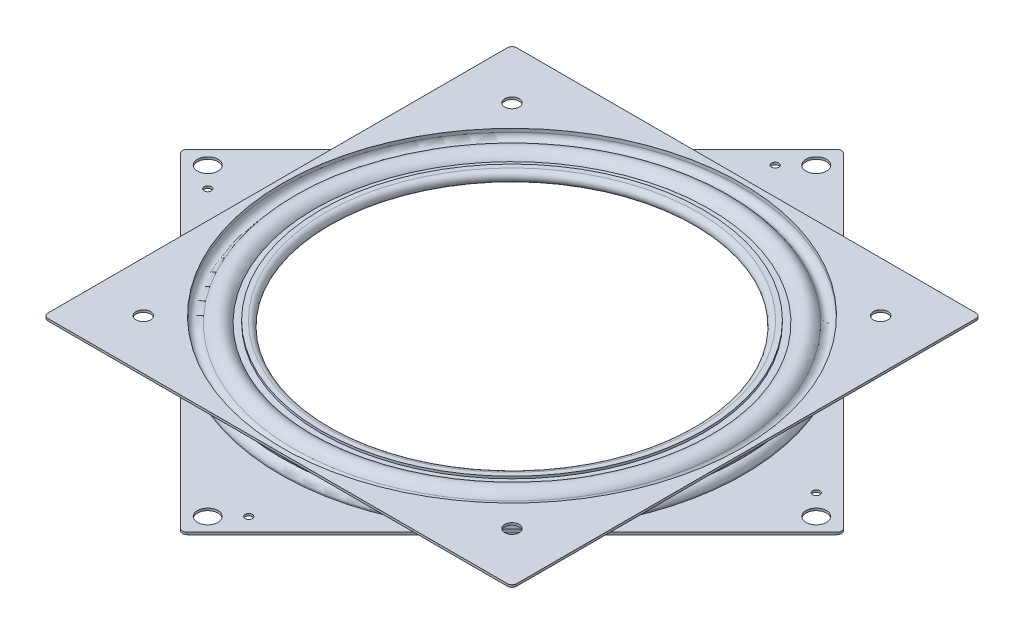
SolidWorks part; units mm, degrees
note: The reader was unsure of these and kept them because the rebuilt part matched: shared geometry of "Sketch3<3>".
material "Galvanized Steel"
ref_plane "Front Plane" through (0, 0, 0) normal (0, 0, 1) x (1, 0, 0)
ref_plane "Top Plane" through (0, 0, 0) normal (0, 1, 0) x (1, 0, 0)
ref_plane "Right Plane" through (0, 0, 0) normal (1, 0, 0) x (0, 0, -1)
sketch "Sketch1" plane through (0, 0, 0) normal (0, 1, 0) x (1, 0, 0)
  line L0 (0, -108.8407) -> (-108.8407, 0) construction
  line L1 (-76.962, 76.962) -> (76.962, 76.962) construction
  line L2 (-76.962, 76.962) -> (-76.962, -76.962) construction
  line L3 (-76.962, -76.962) -> (76.962, -76.962) construction
  line L4 (76.962, 76.962) -> (76.962, -76.962) construction
  line L5 (0, -76.962) -> (0, 76.962) construction
  line L6 (-76.962, 0) -> (76.962, 0) construction
  line L7 (0, -108.8407) -> (108.8407, 0) construction
  line L8 (-108.8407, 0) -> (0, 108.8407) construction
  line L9 (108.8407, 0) -> (0, 108.8407) construction
  line L10 (0, -108.8407) -> (0, 108.8407) construction
  line L11 (-108.8407, 0) -> (108.8407, 0) construction
  line L12 (76.962, -76.962) -> (-76.962, 76.962) construction
  line L13 (76.962, 76.962) -> (-76.962, -76.962) construction
  line L14 (-99.9053, 0) -> (0, 99.9053) construction
  line L19 (-60.5282, 60.5282) -> (60.5282, 60.5282) construction
  line L20 (-60.5282, 60.5282) -> (-60.5282, -60.5282) construction
  line L21 (-60.5282, -60.5282) -> (60.5282, -60.5282) construction
  line L22 (60.5282, 60.5282) -> (60.5282, -60.5282) construction
  line L23 (-99.9053, 0) -> (0, -99.9053) construction
  line L24 (0, 99.9053) -> (99.9053, 0) construction
  line L25 (0, -99.9053) -> (99.9053, 0) construction
  line L26 (-6.7352, 93.1702) -> (0, 99.9053) construction
  line L27 (-99.9053, 0) -> (-93.1702, -6.7352) construction
  line L28 (0, -99.9053) -> (6.7352, -93.1702) construction
  line L29 (93.1702, 6.7352) -> (99.9053, 0) construction
  circle A0 centre (0, 0) radius 59.436 construction
  circle A1 centre (60.5282, -60.5282) radius 2.3813 construction
  circle A2 centre (-60.5282, -60.5282) radius 2.3812 construction
  circle A3 centre (-60.5282, 60.5282) radius 2.3812 construction
  circle A4 centre (60.5282, 60.5282) radius 2.3813 construction
  circle A9 centre (-99.9053, 0) radius 3.3734 construction
  circle A10 centre (0, 99.9053) radius 3.3734 construction
  circle A11 centre (99.9053, 0) radius 3.3734 construction
  circle A12 centre (0, -99.9053) radius 3.3734 construction
  circle A13 centre (-93.1702, -6.7352) radius 1.1922 construction
  circle A14 centre (6.7352, -93.1702) radius 1.1922 construction
  circle A15 centre (93.1702, 6.7352) radius 1.1922 construction
  circle A16 centre (-6.7352, 93.1702) radius 1.1922 construction
  dimension "ID" = 118.872
  dimension "Top Mounting Hole Dia." = 4.7625
  dimension "Bottom Outer Mounting Hole Dia." = 6.7469
  dimension "Bottom Inner Mounting Hole Dia." = 2.3844
  dimension "Length" = 153.924
  dimension "Width" = 153.924
  dimension "Top Mounting Length" = 121.0564
  dimension "Bottom Outer Mounting Length" = 141.2875
  dimension "Bottom Hole Spacing" = 9.525
sketch "Sketch2" plane through (0, 0, 0) normal (0, 0, 1) x (1, 0, 0)
  line L0 (0, 3.937) -> (0, -3.937) construction
  line L1 (-76.962, 3.937) -> (76.962, 3.937) construction
  line L2 (-76.962, 3.937) -> (-76.962, -3.937) construction
  line L3 (-76.962, -3.937) -> (76.962, -3.937) construction
  line L4 (76.962, 3.937) -> (76.962, -3.937) construction
  line L5 (-76.962, 0) -> (76.962, 0) construction
  line L6 (-76.962, 3.2004) -> (76.962, 3.2004) construction
  line L7 (-76.962, -3.2004) -> (76.962, -3.2004) construction
  point P8 (0, 0)
  dimension "Overall Height" = 7.874
  dimension "Plate Thickness" = 0.7366
sketch "Sketch3" plane through (0, 0, 0) normal (0, 0, 1) x (1, 0, 0)
  line L0 (76.962, 3.937) -> (75.3482, 3.937)
  line L1 (-76.962, 3.937) -> (76.962, 3.937) construction
  line L2 (75.3482, 3.937) -> (75.3482, 2.8346)
  line L3 (64.7735, 1.9406) -> (61.2076, 1.9406)
  line L4 (76.962, -3.937) -> (75.3482, -3.937)
  line L5 (-76.962, -3.937) -> (76.962, -3.937) construction
  line L6 (75.3482, -3.937) -> (75.3482, -2.8346)
  line L7 (75.3482, -2.8346) -> (75.3482, 2.8346) construction
  line L8 (64.3585, -0.8661) -> (61.2076, -0.8661)
  line L9 (61.2076, 2.6772) -> (62.7831, 2.6772)
  line L10 (64.3585, -0.8661) -> (75.3482, -0.8661) construction
  line L11 (59.436, 3.937) -> (59.436, -3.937) construction
  line L12 (59.436, 0) -> (-59.436, 0) construction
  line L13 (61.2076, 2.6772) -> (61.2076, 1.9406) construction
  line L14 (76.962, -3.937) -> (76.962, 3.937) construction
  line L15 (68.199, 0) -> (76.962, 0) construction
  line L16 (68.199, 0) -> (59.436, 0) construction
  line L17 (76.962, 3.937) -> (76.962, -3.937) construction
  line L18 (62.7831, -0.8661) -> (62.7831, 2.6772) construction
  line L19 (0, 3.937) -> (0, -3.937) construction
  arc A0 (75.3482, 2.8346) -> (71.6528, 1.8898) centre (73.3797, 2.8346) cw
  circle A1 centre (68.199, 0) radius 3.937 construction
  arc A2 (71.6528, 1.8898) -> (64.7735, 1.9406) centre (68.199, 0) ccw
  arc A3 (75.3482, -2.8346) -> (71.6528, -1.8898) centre (73.3797, -2.8346) ccw
  arc A4 (71.6528, -1.8898) -> (64.3585, -0.8661) centre (68.199, 0) cw
  arc A5 (61.2076, -0.8661) -> (61.2076, 2.6772) centre (61.2076, 0.9055) cw
  point P26 (59.436, 0)
  point P38 (61.9954, 2.6772)
  dimension "D3" = 7.874
  dimension "D4" = 1.9685
  dimension "D1" = 0.7366
  dimension "D2" = 3.5433
  dimension "D5" = 6.6142
  dimension "D6" = 1.6138
revolve "Revolve-Thin1" add sketch "Sketch3" angle 360 about L0
revolve "Revolve-Thin2" add sketch "Sketch3<3>" angle 360 about L0
sketch "Sketch3<3>" plane through (0, 0, 0) normal (0, 0, 1) x (1, 0, 0) same geometry as "Sketch3"
sketch "Sketch4" plane through (0, 3.937, 0) normal (0, 1, 0) x (1, 0, 0)
  line L1 (-76.962, 76.962) -> (76.962, 76.962)
  line L2 (-76.962, 76.962) -> (-76.962, -76.962)
  line L3 (-76.962, -76.962) -> (76.962, -76.962)
  line L4 (76.962, 76.962) -> (76.962, -76.962)
  circle A0 centre (0, 0) radius 75.3482 construction
  circle A1 centre (0, 0) radius 75.3482
extrude "Boss-Extrude1" add sketch "Sketch4" against normal up to vertex (0.7366 mm away) up to point (76.962, 3.2004, 0)
sketch "Sketch5" plane through (0, -3.937, 0) normal (0, -1, 0) x (1, 0, 0)
  line L0 (-108.8407, 0) -> (0, 108.8407)
  line L1 (0, 108.8407) -> (108.8407, 0)
  line L2 (108.8407, 0) -> (0, -108.8407)
  line L3 (0, -108.8407) -> (-108.8407, 0)
  circle A0 centre (0, 0) radius 75.3482 construction
  circle A1 centre (0, 0) radius 75.3482
extrude "Boss-Extrude2" add sketch "Sketch5" against normal up to vertex (0.7366 mm away) up to point (-76.962, -3.2004, 0)
sketch "Sketch6" plane through (0, 0, 0) normal (0, 1, 0) x (1, 0, 0)
  circle A0 centre (-60.5282, 60.5282) radius 2.3812 construction
  circle A1 centre (-60.5282, -60.5282) radius 2.3813 construction
  circle A2 centre (60.5282, -60.5282) radius 2.3813 construction
  circle A3 centre (60.5282, 60.5282) radius 2.3813 construction
  circle A4 centre (-60.5282, 60.5282) radius 2.3812
  circle A5 centre (-60.5282, -60.5282) radius 2.3812
  circle A6 centre (60.5282, -60.5282) radius 2.3813
  circle A7 centre (60.5282, 60.5282) radius 2.3813
extrude "Cut-Extrude1" cut sketch "Sketch6" against normal through all both and the other way through all
sketch "Sketch7" plane through (0, 0, 0) normal (0, 1, 0) x (1, 0, 0)
  line L0 (-99.9053, 0) -> (0, 99.9053) construction
  line L1 (-99.9053, 0) -> (0, -99.9053) construction
  line L2 (0, 99.9053) -> (99.9053, 0) construction
  line L3 (0, -99.9053) -> (99.9053, 0) construction
  line L4 (-99.9053, 0) -> (99.9053, 0) construction
  line L5 (0, 99.9053) -> (0, -99.9053) construction
  line L6 (-108.8407, 0) -> (108.8407, 0) construction
  line L7 (0, -108.8407) -> (0, 108.8407) construction
  circle A0 centre (99.9053, 0) radius 3.3734
  circle A1 centre (0, 99.9053) radius 3.3734
  circle A2 centre (-99.9053, 0) radius 3.3734
  circle A3 centre (0, -99.9053) radius 3.3734
  circle A6 centre (0, -99.9053) radius 3.3734 construction
  circle A7 centre (6.7352, -93.1702) radius 1.1922 construction
  circle A8 centre (6.7352, -93.1702) radius 1.1922
  circle A9 centre (-93.1702, -6.7352) radius 1.1922 construction
  circle A10 centre (-6.7352, 93.1702) radius 1.1922 construction
  circle A11 centre (93.1702, 6.7352) radius 1.1922 construction
  circle A12 centre (-93.1702, -6.7352) radius 1.1922
  circle A13 centre (-6.7352, 93.1702) radius 1.1922
  circle A14 centre (93.1702, 6.7352) radius 1.1922
  point P1 (0, 0)
extrude "Cut-Extrude2" cut sketch "Sketch7" against normal through all both and the other way through all
sketch "Sketch8" plane through (0, 0, 0) normal (0, 0, 1) x (1, 0, 0)
  line L0 (68.199, -3.683) -> (68.199, 3.683)
  arc A1 (68.199, 3.683) -> (68.199, -3.683) centre (68.199, 0) cw
  circle A2 centre (68.199, 0) radius 3.683
  circle A3 centre (68.199, 0) radius 3.683 construction
  dimension "D1" = 0.254
revolve "Revolve1" add sketch "Sketch8" angle 360 about L0
pattern_circular "CirPattern1" [suppressed] count 50 over 360 about axis through (0, 3.937, 0) along (0, -1, 0)
fillet "Fillet1" radius 1.5392 4 edges at (-76.962, 3.5687, -76.962) (76.962, 3.5687, -76.962) (-76.962, 3.5687, 76.962) (76.962, 3.5687, 76.962)
fillet "Fillet2" radius 1.5392 4 edges at (-108.8407, -3.5687, 0) (0, -3.5687, -108.8407) (108.8407, -3.5687, 0) (0, -3.5687, 108.8407)
equation "\"D1@Sketch3\"=\"Plate Thickness@Sketch2\""
equation "\"D2@Sketch3\"=\"Overall Height@Sketch2\"*.45"
equation "\"D5@Sketch3\"=\"Overall Height@Sketch2\"*.84"
equation "\"D4@Sketch3\"=\"D3@Sketch3\"*.25"
equation "\"D3@Revolve-Thin2\"=\"Plate Thickness@Sketch2\""
equation "\"D3@Revolve-Thin1\"=\"Plate Thickness@Sketch2\""
equation "\"D1@Fillet2\"=\"D1@Fillet1\""
equation "\"D1@Fillet1\"=\"Length@Sketch1\"*.01"
